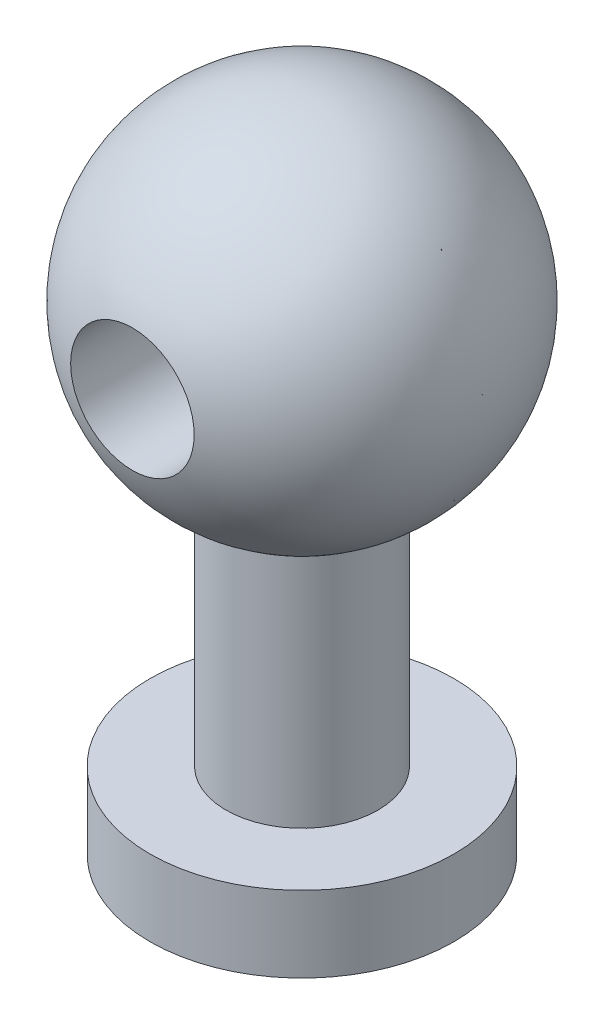
SolidWorks part; units mm, degrees
material "Plain Carbon Steel"
ref_plane "Front Plane" through (0, 0, 0) normal (0, 0, 1) x (1, 0, 0)
ref_plane "Top Plane" through (0, 0, 0) normal (0, 1, 0) x (1, 0, 0)
ref_plane "Right Plane" through (0, 0, 0) normal (1, 0, 0) x (0, 0, -1)
sketch "Sketch1" plane through (0, 0, 0) normal (0, 0, 1) x (1, 0, 0)
  line L0 (0, 0) -> (0, 34.7) construction
  line L1 (0, 0) -> (8, 0)
  line L2 (8, 0) -> (8, 4)
  line L3 (8, 4) -> (4, 4)
  line L4 (4, 4) -> (4, 16.5832)
  line L5 (0, 34.7) -> (0, 0)
  arc A0 (4, 16.5832) -> (0, 34.7) centre (0, 25.2) ccw
  dimension "D2" = 9.5
  dimension "D1" = 25.2
  dimension "D3" = 8
  dimension "D4" = 4
  dimension "D5" = 4
revolve "Revolve1" add sketch "Sketch1" angle 360 about L0
sketch "Sketch2" plane through (0, 0, 0) normal (0, 0, 1) x (1, 0, 0)
  circle A0 centre (0, 25.2) radius 3.25
  dimension "D2" = 6.5
  dimension "D1" = 25.2
extrude "Cut-Extrude1" cut sketch "Sketch2" against normal mid plane 40
